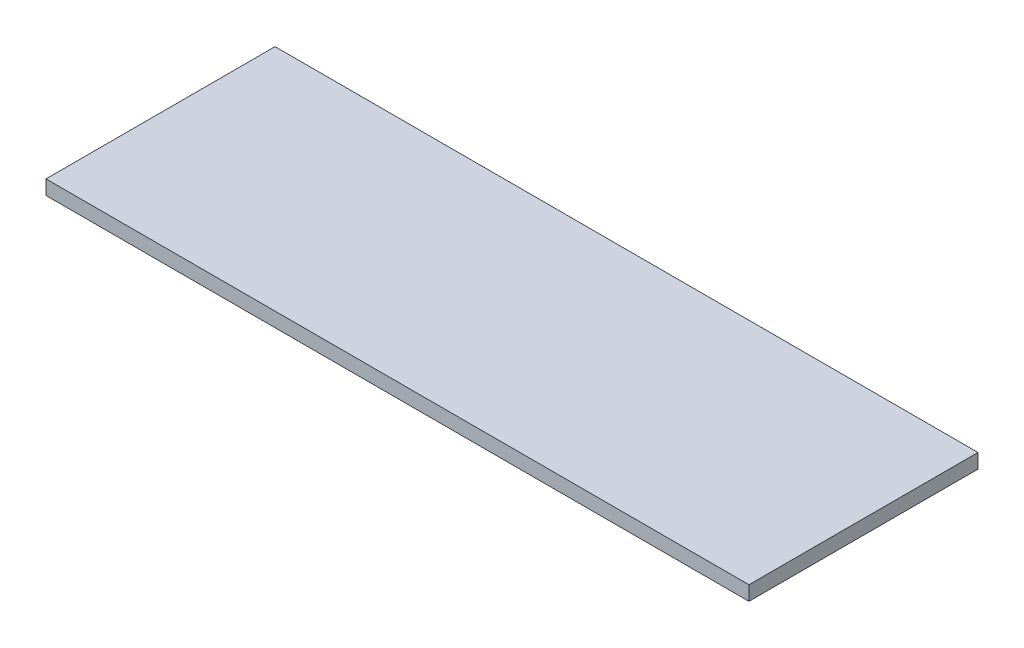
SolidWorks part; units mm, degrees
ref_plane "前视基准面" through (0, 0, 0) normal (0, 0, 1) x (1, 0, 0)
ref_plane "上视基准面" through (0, 0, 0) normal (0, 1, 0) x (1, 0, 0)
ref_plane "右视基准面" through (0, 0, 0) normal (1, 0, 0) x (0, 0, -1)
sketch "草图1" plane through (0, 0, 0) normal (0, 1, 0) x (1, 0, 0)
  line L1 (0, 0) -> (244, 0)
  line L2 (0, 0) -> (0, -79.5)
  line L3 (0, -79.5) -> (244, -79.5)
  line L4 (244, 0) -> (244, -79.5)
  dimension "D1" = 244
  dimension "D2" = 79.5
extrude "凸台-拉伸1" add sketch "草图1" along normal blind 5
